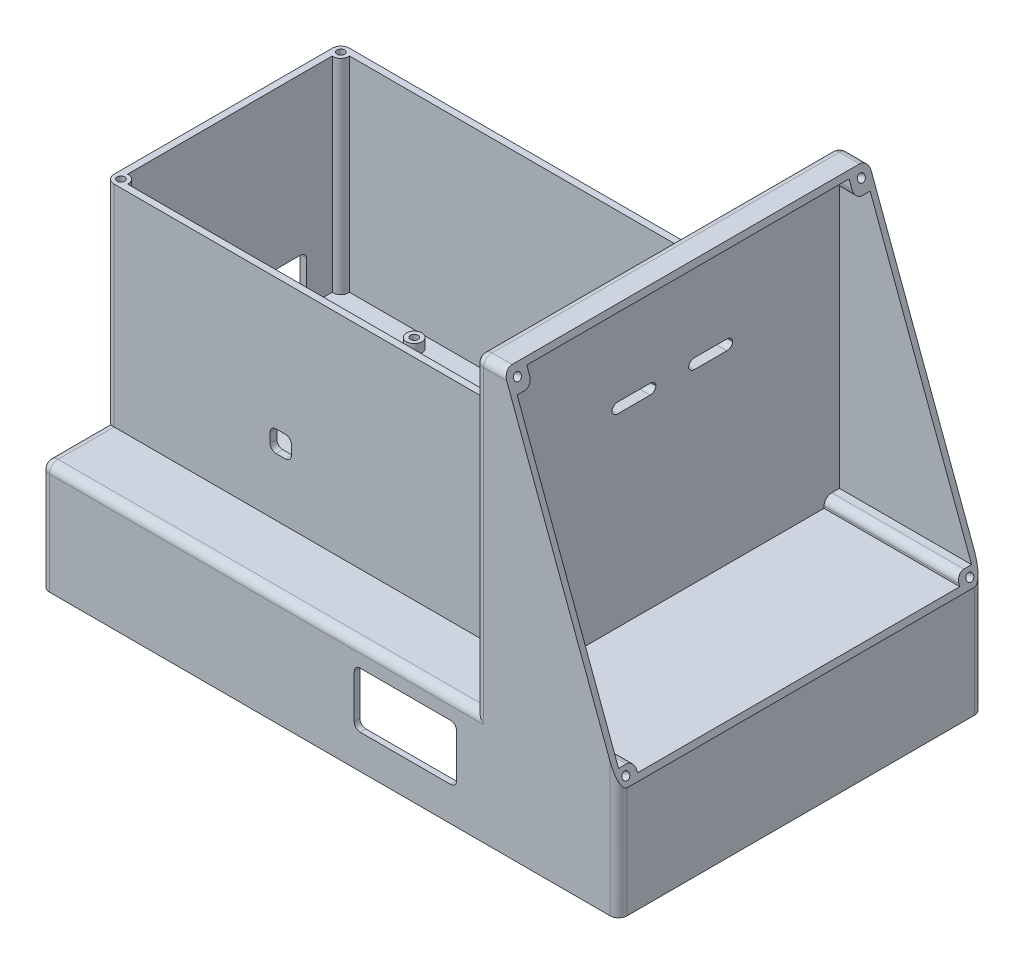
SolidWorks part; units mm, degrees
note: The reader was unsure of these and kept them because the rebuilt part matched: shared geometry of "Sketch1<6>", "Sketch29<4>", "Sketch29<5>".
ref_plane "Front Plane" through (0, 0, 0) normal (0, 0, 1) x (1, 0, 0)
ref_plane "Top Plane" through (0, 0, 0) normal (0, 1, 0) x (1, 0, 0)
ref_plane "Right Plane" through (0, 0, 0) normal (1, 0, 0) x (0, 0, -1)
sketch "Sketch1" plane through (0, 0, 0) normal (0, 1, 0) x (1, 0, 0)
  line L1 (0, 0) -> (125.286, 0)
  line L2 (0, 0) -> (0, -66.104)
  line L3 (0, -66.104) -> (125.286, -66.104)
  line L4 (125.286, 0) -> (125.286, -66.104)
  line L5 (-2, 2) -> (127.286, 2)
  line L6 (-2, 2) -> (-2, -68.104)
  line L7 (-2, -68.104) -> (127.286, -68.104)
  line L8 (127.286, 2) -> (127.286, -68.104)
  line L9 (2.572, -2.572) -> (122.714, -2.572) construction
  line L10 (2.572, -2.572) -> (2.572, -63.532) construction
  line L11 (2.572, -63.532) -> (122.714, -63.532) construction
  line L12 (122.714, -2.572) -> (122.714, -63.532) construction
  dimension "D1" = 4.572
  dimension "D2" = 60.96
  dimension "D3" = 2
  dimension "D4" = 2
  dimension "D5" = 2
  dimension "D6" = 2
  dimension "D7" = 4.572
  dimension "D8" = 120.142
  dimension "D9" = 4.572
  dimension "D10" = 4.572
extrude "Boss-Extrude1" add sketch "Sketch1" against normal blind 1.7 contours L6 L7 L8 L5
extrude "Boss-Extrude2" add sketch "Sketch1<6>" along normal blind 60.96 contours L6 L7 L8 L5 | L2 L3 L4 L1
sketch "Sketch1<6>" plane through (0, 0, 0) normal (0, 1, 0) x (1, 0, 0) same geometry as "Sketch1"
sketch "Sketch3" plane through (0, 0, 0) normal (0, 1, 0) x (1, 0, 0)
  line L1 (2.572, -2.572) -> (122.714, -2.572)
  line L2 (2.572, -2.572) -> (2.572, -63.532)
  line L3 (2.572, -63.532) -> (122.714, -63.532)
  line L4 (122.714, -2.572) -> (122.714, -63.532)
  line L10 (-2, 2) -> (-2, -68.104) construction
  line L11 (-2, 2) -> (127.286, 2) construction
  dimension "D1" = 120.142
  dimension "D2" = 60.96
  dimension "D3" = 4.572
  dimension "D4" = 4.572
sketch "Sketch4" plane through (0, -1.7, 0) normal (0, -1, 0) x (1, 0, 0)
  line L0 (2.572, 2.572) -> (2.572, 63.532) construction
  line L1 (2.572, 63.532) -> (122.714, 63.532) construction
  line L3 (2.572, 2.572) -> (122.714, 2.572) construction
  line L4 (122.714, 2.572) -> (122.714, 63.532) construction
  circle A0 centre (25.432, 50.832) radius 1.397
  circle A1 centre (26.702, 4.858) radius 1.397
  circle A2 centre (78.01, 20.352) radius 1.397
  circle A3 centre (108.49, 50.832) radius 1.397
  circle A4 centre (105.95, 4.858) radius 1.397
  circle A5 centre (87.154, 45.752) radius 1.397
  circle A6 centre (25.432, 50.832) radius 2.286
  circle A7 centre (26.702, 4.858) radius 2.286
  circle A8 centre (78.01, 20.352) radius 2.286
  circle A9 centre (105.95, 4.858) radius 2.286
  circle A10 centre (87.154, 45.752) radius 2.286
  circle A11 centre (108.49, 50.832) radius 2.286
  dimension "D1" = 2.794
  dimension "D5" = 2.794
  dimension "D8" = 2.794
  dimension "D9" = 2.794
  dimension "D10" = 2.794
  dimension "D15" = 2.794
  dimension "D20" = 4.572
  dimension "D21" = 4.572
  dimension "D22" = 4.572
  dimension "D23" = 4.572
  dimension "D24" = 4.572
  dimension "D25" = 4.572
  dimension "D2" = 90
  dimension "D3" = 12.7
  dimension "D4" = 22.86
  dimension "D6" = 2.286
  dimension "D7" = 24.13
  dimension "D11" = 17.78
  dimension "D12" = 44.704
  dimension "D13" = 2.286
  dimension "D14" = 16.764
  dimension "D16" = 17.78
  dimension "D17" = 35.56
  dimension "D18" = 12.7
  dimension "D19" = 14.224
sketch "Sketch5" plane through (0, -1.7, 0) normal (0, -1, 0) x (1, 0, 0)
  line L0 (-2, 68.104) -> (127.286, 68.104) construction
  line L2 (-2, -2) -> (-2, 68.104) construction
  line L3 (-2, -2) -> (127.286, -2) construction
  line L4 (127.286, -2) -> (127.286, 68.104) construction
  circle A0 centre (0.286, 65.818) radius 2.286
  circle A1 centre (0.286, 0.286) radius 2.286
  circle A2 centre (125, 65.818) radius 2.286
  circle A3 centre (125, 0.286) radius 2.286
  dimension "D1" = 4.572
  dimension "D2" = 4.572
  dimension "D3" = 4.572
  dimension "D4" = 4.572
extrude "Boss-Extrude3" add sketch "Sketch5" against normal up to vertex (62.66 mm away)
extrude "Boss-Extrude4" add sketch "Sketch4" against normal blind 4.572 contours A6 | A7 | A8 | A10 | A11 | A9
hole_wizard "#4-40 Tapped Hole1" positions "Sketch15" profile "Sketch7" tap size "#4-40" standard "ANSI Inch"
sketch "Sketch15" plane through (0, 2.872, 0) normal (0, 1, 0) x (1, 0, 0)
  point P0 (26.702, -4.858)
  point P3 (78.01, -20.352)
  point P6 (105.95, -4.858)
  point P9 (87.154, -45.752)
  point P12 (108.49, -50.832)
  point P15 (25.432, -50.832)
cosmetic thread "Hole Thread1" parameters "D1"=5.588, "D2"=2.8448
cosmetic thread "Hole Thread2" parameters "D1"=5.588, "D2"=2.8448
cosmetic thread "Hole Thread3" parameters "D1"=5.588, "D2"=2.8448
cosmetic thread "Hole Thread4" parameters "D1"=5.588, "D2"=2.8448
cosmetic thread "Hole Thread5" parameters "D1"=5.588, "D2"=2.8448
cosmetic thread "Hole Thread6" parameters "D1"=5.588, "D2"=2.8448
sketch "Sketch7" plane through (26.702, 2.872, 4.858) normal (1, 0, 0) x (0, 0, 1)
  line L0 (0, 0) -> (0, 2.872)
  line L1 (0, 2.872) -> (1.1303, 2.1928)
  line L2 (1.1303, 2.1928) -> (1.1303, 0)
  line L5 (1.1303, 0) -> (0, 0)
  line L10 (0, 2.872) -> (-1.1303, 2.1928) construction
  line L11 (0, -6.35) -> (0, 107.95) construction
  dimension "Tap Drill Dia." = 2.2606
  dimension "Tap Drill Depth" = 2.872
  dimension "Drill Angle" = 118
hole_wizard "#4-40 Tapped Hole2" positions "Sketch31" profile "Sketch10" tap size "#4-40" standard "ANSI Inch"
sketch "Sketch31" plane through (0, 60.96, 0) normal (0, 1, 0) x (1, 0, 0)
  point P0 (0.286, -0.286)
  point P3 (0.286, -65.7963)
  point P5 (125, -65.818)
  point P8 (125, -0.286)
cosmetic thread "Hole Thread11" parameters "D1"=5.588, "D2"=2.8448
cosmetic thread "Hole Thread12" parameters "D1"=5.588, "D2"=2.8448
cosmetic thread "Hole Thread13" parameters "D1"=5.588, "D2"=2.8448
cosmetic thread "Hole Thread14" parameters "D1"=5.588, "D2"=2.8448
sketch "Sketch10" plane through (0.286, 60.96, 0.286) normal (1, 0, 0) x (0, 0, 1)
  line L0 (0, 0) -> (0, 7.62)
  line L1 (0, 7.62) -> (1.1303, 6.9408)
  line L2 (1.1303, 6.9408) -> (1.1303, 0)
  line L5 (1.1303, 0) -> (0, 0)
  line L10 (0, 7.62) -> (-1.1303, 6.9408) construction
  line L11 (0, -6.35) -> (0, 107.95) construction
  dimension "Tap Drill Dia." = 2.2606
  dimension "Tap Drill Depth" = 7.62
  dimension "Drill Angle" = 118
fillet "Fillet1" radius 2.54 2 edges at (-2, 29.63, -2) (-2, 29.63, 68.104)
sketch "Sketch16" plane through (-2, 0, 0) normal (-1, 0, 0) x (0, 0, 1)
  line L0 (2.572, 0) -> (2.572, 3.4402) construction
  line L1 (2.572, 58.928) -> (63.532, 58.928) construction
  line L2 (2.572, 58.928) -> (2.572, 2.872) construction
  line L3 (2.572, 2.872) -> (63.532, 2.872) construction
  line L4 (63.532, 58.928) -> (63.532, 2.872) construction
  line L5 (2.572, 0) -> (63.532, 0) construction
  line L6 (63.532, 0.3799) -> (63.532, 2.4643) construction
  line L7 (65.564, -1.7) -> (65.564, 60.96) construction
  line L8 (0.54, 60.96) -> (0.54, -1.7) construction
  line L11 (0.54, 60.96) -> (65.564, 60.96) construction
  line L12 (10.192, 14.302) -> (22.13, 14.302)
  line L13 (10.192, 14.302) -> (10.192, 2.872)
  line L14 (10.192, 2.872) -> (22.13, 2.872)
  line L15 (22.13, 14.302) -> (22.13, 2.872)
  line L16 (42.704, 14.048) -> (52.102, 14.048)
  line L17 (42.704, 14.048) -> (42.704, 2.872)
  line L18 (42.704, 2.872) -> (52.102, 2.872)
  line L19 (52.102, 14.048) -> (52.102, 2.872)
  line L20 (42.704, 20.398) -> (63.532, 20.398)
  line L21 (42.704, 20.398) -> (42.704, 15.572)
  line L22 (42.704, 15.572) -> (63.532, 15.572)
  line L23 (63.532, 20.398) -> (63.532, 15.572)
  dimension "D1" = 2.032
  dimension "D2" = 2.032
  dimension "D4" = 2.032
  dimension "D5" = 7.62
  dimension "D6" = 11.938
  dimension "D7" = 11.43
  dimension "D8" = 9.398
  dimension "D9" = 11.176
  dimension "D10" = 11.43
  dimension "D11" = 1.524
  dimension "D12" = 6.35
sketch "Sketch17" plane through (127.286, 0, 0) normal (1, 0, 0) x (0, 0, -1)
  line L1 (-63.532, 58.928) -> (-2.572, 58.928) construction
  line L2 (-63.532, 58.928) -> (-63.532, 2.872) construction
  line L3 (-63.532, 2.872) -> (-2.572, 2.872) construction
  line L4 (-2.572, 58.928) -> (-2.572, 2.872) construction
  line L5 (-48.292, 58.166) -> (-35.084, 58.166)
  line L6 (-48.292, 58.166) -> (-48.292, 55.118)
  line L7 (-48.292, 55.118) -> (-35.084, 55.118)
  line L8 (-35.084, 58.166) -> (-35.084, 55.118)
  line L9 (-25.432, 58.166) -> (-12.224, 58.166)
  line L10 (-25.432, 58.166) -> (-25.432, 55.118)
  line L11 (-25.432, 55.118) -> (-12.224, 55.118)
  line L12 (-12.224, 58.166) -> (-12.224, 55.118)
  dimension "D1" = 15.24
  dimension "D2" = 13.208
  dimension "D3" = 3.048
  dimension "D4" = 9.652
  dimension "D5" = 13.208
  dimension "D6" = 3.048
  dimension "D7" = 1.524
  dimension "D8" = 1.524
sketch "Sketch18" plane through (0, 0, -2) normal (0, 0, -1) x (-1, 0, 0)
  line L0 (-0.54, 60.96) -> (-127.286, 60.96) construction
  line L1 (-122.714, 2.872) -> (-2.572, 2.872)
  line L2 (-122.714, 2.872) -> (-122.714, 58.928)
  line L3 (-122.714, 58.928) -> (-2.572, 58.928)
  line L4 (-2.572, 2.872) -> (-2.572, 58.928)
  line L6 (-127.286, -1.7) -> (-127.286, 60.96) construction
  dimension "D1" = 120.142
  dimension "D2" = 2.032
  dimension "D3" = 56.056
  dimension "D4" = 4.572
sketch "Sketch19" plane through (0, 0, 68.104) normal (0, 0, 1) x (1, 0, 0)
  line L1 (2.572, 58.928) -> (122.714, 58.928) construction
  line L2 (2.572, 58.928) -> (2.572, 2.872) construction
  line L3 (2.572, 2.872) -> (122.714, 2.872) construction
  line L4 (122.714, 58.928) -> (122.714, 2.872) construction
  line L5 (47.022, 21.922) -> (53.372, 21.922)
  line L6 (47.022, 21.922) -> (47.022, 15.572)
  line L7 (47.022, 15.572) -> (53.372, 15.572)
  line L8 (53.372, 21.922) -> (53.372, 15.572)
  dimension "D1" = 44.45
  dimension "D2" = 6.35
  dimension "D3" = 6.35
  dimension "D4" = 12.7
extrude "Cut-Extrude1" cut sketch "Sketch16" against normal blind 2.54 contours L19 L16 L17 L18 | L23 L20 L21 L22 | L12 L15 L14 L13
extrude "Cut-Extrude2" cut sketch "Sketch19" against normal blind 2.54 contours L5 L8 L7 L6
extrude "Cut-Extrude3" cut sketch "Sketch17" against normal blind 2.54 contours L12 L9 L10 L11 | L6 L7 L8 L5
sketch "Sketch29" plane through (0, -1.7, 0) normal (0, -1, 0) x (1, 0, 0)
  line L0 (-2, 0.54) -> (-2, 65.564) construction
  line L1 (-0.3, 85.63) -> (168.356, 85.63)
  line L2 (-0.3, 85.63) -> (-0.3, -19.526)
  line L3 (-0.3, -19.526) -> (168.356, -19.526)
  line L4 (168.356, 85.63) -> (168.356, -19.526)
  line L12 (0.54, 68.104) -> (127.286, 68.104) construction
  line L13 (-2, -2) -> (127.286, -2) construction
  line L15 (-2, 87.33) -> (170.056, 87.33)
  line L16 (-2, 87.33) -> (-2, -21.226)
  line L17 (-2, -21.226) -> (170.056, -21.226)
  line L18 (170.056, 87.33) -> (170.056, -21.226)
  circle A0 centre (0.286, 85.044) radius 2.286
  circle A1 centre (0.286, -18.94) radius 2.286
  circle A2 centre (167.77, -18.94) radius 2.286
  circle A3 centre (167.77, 85.044) radius 2.286
  dimension "D3" = 4.572
  dimension "D7" = 4.572
  dimension "D10" = 4.572
  dimension "D11" = 4.572
  dimension "D1" = 168.656
  dimension "D2" = 105.156
  dimension "D4" = 17.526
  dimension "D5" = 17.526
  dimension "D6" = 1.7
  dimension "0.18" = 1.7
  dimension "D8" = 1.7
  dimension "D9" = 1.7
extrude "Boss-Extrude8" add sketch "Sketch29" along normal blind 1.7 contours L16 L17 L18 L15
extrude "Boss-Extrude9" add sketch "Sketch29<4>" along normal blind 33.02 contours L16 L17 L18 L15 | L2 L3 L4 L1
sketch "Sketch29<4>" plane through (0, -1.7, 0) normal (0, -1, 0) x (1, 0, 0) same geometry as "Sketch29"
extrude "Boss-Extrude10" add sketch "Sketch29<5>" along normal blind 33.02 contours A3 | A2 | A1 | A0
sketch "Sketch29<5>" plane through (0, -1.7, 0) normal (0, -1, 0) x (1, 0, 0) same geometry as "Sketch29"
hole_wizard "#4-40 Tapped Hole5" positions "Sketch39" profile "Sketch38" tap size "#4-40" standard "ANSI Inch"
sketch "Sketch39" plane through (0, -34.72, 0) normal (0, -1, 0) x (-1, 0, 0)
  point P0 (-167.77, 18.94)
  point P3 (-167.77, -85.044)
  point P6 (-0.286, -85.044)
  point P9 (-0.286, 18.94)
sketch "Sketch38" plane through (167.77, -34.72, -18.94) normal (1, 0, 0) x (0, 0, -1)
  line L0 (0, 0) -> (0, 7.62)
  line L1 (0, 7.62) -> (1.1303, 6.9408)
  line L2 (1.1303, 6.9408) -> (1.1303, 0)
  line L5 (1.1303, 0) -> (0, 0)
  line L10 (0, 7.62) -> (-1.1303, 6.9408) construction
  line L11 (0, -6.35) -> (0, 107.95) construction
  dimension "Tap Drill Dia." = 2.2606
  dimension "Tap Drill Depth" = 7.62
  dimension "Drill Angle" = 118
cosmetic thread "Hole Thread19" parameters "D1"=5.588, "D2"=2.8448
cosmetic thread "Hole Thread20" parameters "D1"=5.588, "D2"=2.8448
cosmetic thread "Hole Thread21" parameters "D1"=5.588, "D2"=2.8448
cosmetic thread "Hole Thread22" parameters "D1"=5.588, "D2"=2.8448
fillet "Fillet4" radius 2.54 4 edges at (-2, -1.7, -10.343) (-2, -1.7, 76.447) (-2, -18.21, -21.226) (-2, -18.21, 87.33)
fillet "Fillet9" radius 1.778 24 edges at (-1, 14.302, 10.192) (-1, 2.872, 10.192) (-1, 14.048, 52.102) (126.286, 55.118, 12.224) (126.286, 58.166, 12.224) (126.286, 58.166, 25.432) (126.286, 55.118, 25.432) (126.286, 58.166, 48.292) (126.286, 58.166, 35.084) (126.286, 55.118, 35.084) (126.286, 55.118, 48.292) (47.022, 21.922, 67.104) (53.372, 21.922, 67.104) (53.372, 15.572, 67.104) (47.022, 15.572, 67.104) (-1, 20.398, 63.532) (-1, 15.572, 63.532) (-1, 2.872, 52.102) (-1, 15.572, 42.704) (-1, 20.398, 42.704) (-1, 14.048, 42.704) (-1, 2.872, 42.704) (-1, 2.872, 22.13) (-1, 14.302, 22.13)
sketch "Sketch41" plane through (-2, 0, 0) normal (-1, 0, 0) x (0, 0, 1)
  line L0 (-18.686, -4.24) -> (-18.686, -34.72) construction
  line L1 (-15.257, -3.81) -> (81.263, -3.81) construction
  line L2 (-15.257, -3.81) -> (-15.257, -33.02) construction
  line L3 (-15.257, -33.02) -> (81.263, -33.02) construction
  line L4 (81.263, -3.81) -> (81.263, -33.02) construction
  line L7 (84.79, -34.72) -> (84.79, -4.24) construction
  line L8 (84.79, -34.72) -> (-18.686, -34.72) construction
  line L10 (-0.017, -17.145) -> (55.863, -17.145)
  line L11 (-0.017, -17.145) -> (-0.017, -24.765)
  line L12 (-0.017, -24.765) -> (55.863, -24.765)
  line L13 (55.863, -17.145) -> (55.863, -24.765)
  dimension "D1" = 29.21
  dimension "D2" = 96.52
  dimension "D3" = 3.429
  dimension "D4" = 3.527
  dimension "D5" = 1.7
  dimension "D6" = 55.88
  dimension "D7" = 7.62
  dimension "D8" = 25.4
  dimension "D9" = 8.255
extrude "Cut-Extrude4" cut sketch "Sketch41" against normal blind 2.54
fillet "Fillet10" radius 1.778 4 edges at (-1.15, -17.145, 55.863) (-1.15, -24.765, 55.863) (-1.15, -17.145, -0.017) (-1.15, -24.765, -0.017)
sketch "Sketch42" plane through (0, 0, 87.33) normal (0, 0, 1) x (1, 0, 0)
  line L0 (0.54, -34.72) -> (170.056, -34.72) construction
  line L1 (91.316, -8.05) -> (121.796, -8.05)
  line L2 (91.316, -8.05) -> (91.316, -24.56)
  line L3 (91.316, -24.56) -> (121.796, -24.56)
  line L4 (121.796, -8.05) -> (121.796, -24.56)
  line L6 (170.056, -34.72) -> (170.056, -1.7) construction
  dimension "D1" = 16.51
  dimension "D2" = 10.16
  dimension "D3" = 30.48
  dimension "D4" = 48.26
extrude "Cut-Extrude5" cut sketch "Sketch42" against normal blind 2.54 contours L1 L4 L3 L2
fillet "Fillet11" radius 1.778 4 edges at (91.316, -8.05, 86.48) (121.796, -8.05, 86.48) (121.796, -24.56, 86.48) (91.316, -24.56, 86.48)
sketch "Sketch43" plane through (127.286, 0, 0) normal (1, 0, 0) x (0, 0, -1)
  line L0 (-68.104, -1.7) -> (-68.104, 60.96) construction
  line L1 (-85.63, 88.701) -> (-68.104, 88.701)
  line L2 (-85.63, 88.701) -> (-85.63, -1.7)
  line L3 (-85.63, -1.7) -> (-68.104, -1.7)
  line L4 (-68.104, 88.701) -> (-68.104, -1.7)
  line L5 (2, -1.7) -> (-68.104, -1.7) construction
  line L6 (2, -1.7) -> (2, 60.96) construction
  line L7 (2, 88.701) -> (19.526, 88.701)
  line L8 (2, 88.701) -> (2, -1.7)
  line L9 (2, -1.7) -> (19.526, -1.7)
  line L10 (19.526, 88.701) -> (19.526, -1.7)
  line L13 (2, 60.96) -> (-68.104, 60.96) construction
  line L14 (-68.104, 88.701) -> (2, 88.701)
  line L15 (-68.104, 88.701) -> (-68.104, 60.96)
  line L16 (-68.104, 60.96) -> (2, 60.96)
  line L17 (2, 88.701) -> (2, 60.96)
  line L19 (-87.33, -34.72) -> (-87.33, -1.7) construction
  line L20 (21.226, -34.72) -> (21.226, -1.7) construction
  dimension "D1" = 1.7
  dimension "D2" = 1.7
  dimension "D3" = 90.401
extrude "Boss-Extrude11" add sketch "Sketch43" along normal blind 1.7
sketch "Sketch44" plane through (0, 0, -19.526) normal (0, 0, -1) x (-1, 0, 0)
  line L0 (-136.4392, 88.701) -> (-170.056, -1.7)
  line L1 (-136.4392, 88.701) -> (-127.286, 88.701)
  line L3 (-127.286, 88.701) -> (-127.286, -1.7) construction
  line L4 (-127.286, 88.701) -> (-127.286, -1.7)
  line L5 (-127.286, -1.7) -> (-170.056, -1.7)
  dimension "D1" = 96.4491
  dimension "D2" = 90.401
extrude "Boss-Extrude12" add sketch "Sketch44" along normal blind 1.7 contours L0 L5 L4 L1
sketch "Sketch45" plane through (0, 0, 85.63) normal (0, 0, 1) x (1, 0, 0)
  line L0 (127.286, 88.701) -> (136.4392, 88.701)
  line L1 (136.4392, 88.701) -> (170.056, -1.7)
  line L2 (170.056, -1.7) -> (127.286, -1.7)
  line L3 (127.286, -1.7) -> (127.286, 88.701)
  line L4 (136.4392, 88.701) -> (170.056, -1.7) construction
extrude "Boss-Extrude13" add sketch "Sketch45" along normal blind 1.7 contours L1 L2 L3 L0
ref_plane "Plane1" through (148.8417, 55.3488, 0) normal (0.9373, 0.3485, 0) x (0, 0, -1)
sketch "Sketch48" plane through (0, 88.701, 0) normal (0, 1, 0) x (1, 0, 0)
  line L1 (127.286, 21.226) -> (136.4392, 21.226)
  line L2 (127.286, 21.226) -> (127.286, -87.33)
  line L3 (127.286, -87.33) -> (136.4392, -87.33)
  line L4 (136.4392, 21.226) -> (136.4392, -87.33)
extrude "Boss-Extrude17" add sketch "Sketch48" along normal blind 1.7 separate body
sketch "Sketch50" plane through (128.986, 0, 0) normal (1, 0, 0) x (0, 0, -1)
  line L0 (-85.63, 88.701) -> (19.526, 88.701) construction
  line L5 (-85.63, 88.701) -> (-85.63, -1.7) construction
  line L6 (-83.344, 2.872) -> (-85.63, 2.872)
  line L7 (-85.63, 88.701) -> (-85.63, -1.7) construction
  line L8 (-81.058, 0.586) -> (-81.058, -1.7)
  line L9 (-85.63, 88.701) -> (-85.63, -1.7) construction
  line L10 (-81.058, 86.415) -> (-81.058, 88.701)
  line L11 (-85.63, -1.7) -> (19.526, -1.7) construction
  line L12 (19.526, 88.701) -> (19.526, -1.7) construction
  line L13 (14.954, 0.586) -> (14.954, -1.7)
  line L14 (17.24, 2.872) -> (19.526, 2.872)
  line L15 (-87.33, 88.701) -> (21.226, 88.701) construction
  line L16 (19.526, 88.701) -> (19.526, -1.7) construction
  line L17 (14.954, 86.415) -> (14.954, 88.701)
  line L18 (-83.344, 84.129) -> (-85.63, 84.129)
  line L19 (-85.63, 88.701) -> (-85.63, -1.7) construction
  line L20 (17.24, 84.129) -> (19.526, 84.129)
  line L21 (-85.63, 86.415) -> (-85.63, 88.701)
  line L22 (-85.63, 88.701) -> (-83.344, 88.701)
  line L23 (17.24, 88.701) -> (19.526, 88.701)
  line L24 (19.526, 88.701) -> (19.526, 86.415)
  circle A0 centre (-83.344, 0.586) radius 2.286
  circle A2 centre (17.24, 0.586) radius 2.286
  circle A3 centre (17.24, 86.415) radius 2.286
  circle A4 centre (-83.344, 86.415) radius 2.286
  dimension "D3" = 4.572
  dimension "D1" = 4.572
  dimension "D2" = 4.572
  dimension "D4" = 4.572
extrude "Boss-Extrude19" add sketch "Sketch50" along normal blind 61.39
other "SurfaceCut6"
fillet "Fillet12" radius 2.54 11 edges at (-1.2561, -2.4439, 86.5861) (-1.2561, -2.4439, -20.4821) (63.913, -1.7, 87.33) (63.913, -1.7, -21.226) (127.286, 44.3505, -21.226) (127.286, 90.401, 33.052) (127.286, 44.3505, 87.33) (170.056, -18.21, 87.33) (170.056, -18.21, -21.226) (131.5465, 90.401, -21.226) (131.5465, 90.401, 87.33)
sketch "Sketch53" plane through (128.986, 0, 0) normal (1, 0, 0) x (0, 0, -1)
  line L0 (-81.058, 0) -> (14.954, 0)
  line L2 (-81.058, -1.7) -> (14.954, -1.7) construction
  line L3 (-81.058, 0.586) -> (-81.058, -1.7) construction
  line L4 (14.954, 0.586) -> (14.954, -1.7) construction
  line L5 (-81.058, 0) -> (-81.058, -1.7)
  line L6 (-81.058, -1.7) -> (14.954, -1.7)
  line L7 (14.954, -1.7) -> (14.954, 0)
  dimension "D1" = 1.7
extrude "Boss-Extrude20" add sketch "Sketch53" along normal up to surface (40.4378 mm away)
sketch "Sketch70" plane through (148.8417, 55.3488, 0) normal (0.9373, 0.3485, 0) x (0, 0, -1)
  line L0 (-84.79, 37.3973) -> (18.686, 37.3973) construction
  line L1 (-87.33, 34.6874) -> (-87.33, -53.5781) construction
  line L2 (21.226, 34.6874) -> (21.226, -53.5781) construction
  line L3 (-84.79, -60.8655) -> (18.686, -60.8655) construction
  circle A0 centre (-84.282, 34.3493) radius 1.778
  circle A1 centre (18.178, 34.3493) radius 1.778
  circle A2 centre (18.178, -58.3255) radius 1.778
  circle A3 centre (-84.282, -58.3255) radius 1.778
  point P0 (-84.282, 34.3493)
  point P6 (18.178, 34.3493)
  point P8 (18.178, -58.3255)
  point P10 (-84.282, -58.3255)
  dimension "D3" = 3.556
  dimension "D6" = 3.556
  dimension "D9" = 3.556
  dimension "D12" = 3.556
  dimension "D1" = 3.048
  dimension "D2" = 3.048
  dimension "D4" = 3.048
  dimension "D5" = 3.048
  dimension "D7" = 3.048
  dimension "D8" = 2.54
  dimension "D10" = 2.54
  dimension "D11" = 3.048
hole_wizard "#4-40 Tapped Hole8" positions "Sketch70" profile "Sketch71" tap size "#4-40" standard "ANSI Inch"
cosmetic thread "Hole Thread31" parameters "D1"=10.668, "D2"=2.8448
cosmetic thread "Hole Thread32" parameters "D1"=10.668, "D2"=2.8448
cosmetic thread "Hole Thread33" parameters "D1"=10.668, "D2"=2.8448
cosmetic thread "Hole Thread34" parameters "D1"=10.668, "D2"=2.8448
sketch "Sketch71" plane through (136.8694, 87.5441, 84.282) normal (0, 0, 1) x (-0.3485, 0.9373, 0)
  line L0 (0, 0) -> (0, 8.2992)
  line L1 (0, 8.2992) -> (1.1303, 7.62)
  line L2 (1.1303, 7.62) -> (1.1303, 0)
  line L5 (1.1303, 0) -> (0, 0)
  line L10 (0, 8.2992) -> (-1.1303, 7.62) construction
  line L11 (0, -6.35) -> (0, 107.95) construction
  dimension "Tap Drill Dia." = 2.2606
  dimension "Tap Drill Depth" = 7.62
  dimension "Drill Angle" = 118
